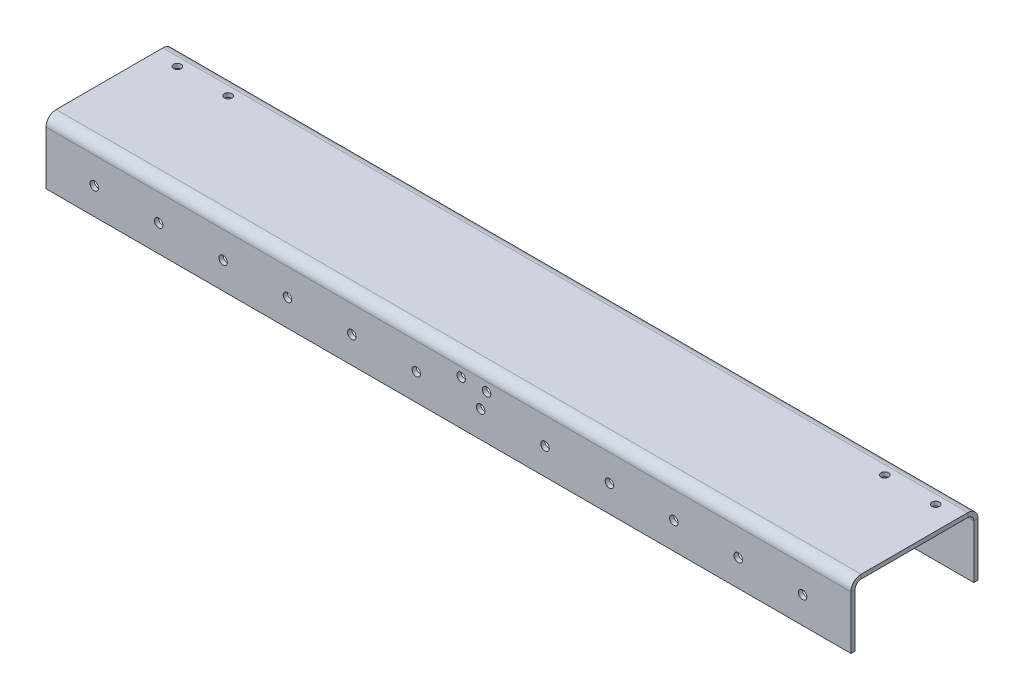
SolidWorks part; units mm, degrees
note: The reader was unsure of these and kept them because the rebuilt part matched: flange length of "Edge-Flange1".
material "Plain Carbon Steel"
ref_plane "Front Plane" through (0, 0, 0) normal (0, 0, 1) x (1, 0, 0)
ref_plane "Top Plane" through (0, 0, 0) normal (0, 1, 0) x (1, 0, 0)
ref_plane "Right Plane" through (0, 0, 0) normal (1, 0, 0) x (0, 0, -1)
sketch "Sketch1" plane through (0, 0, 0) normal (0, 1, 0) x (1, 0, 0)
  line L1 (-950, -150) -> (950, -150)
  line L2 (-950, -150) -> (-950, 150)
  line L3 (-950, 150) -> (950, 150)
  line L4 (950, -150) -> (950, 150)
  line L5 (-950, -150) -> (950, 150) construction
  line L6 (-950, 150) -> (950, -150) construction
  point P0 (0, 0)
  dimension "D1" = 1900
  dimension "D2" = 300
base flange "Base-Flange1" sketch "Sketch1" thickness 10 reverse thickness direction no parameters "D1"=3
edge flange "Edge-Flange1" sketch "Sketch12" flange profiles "Sketch12", "Sketch13" flange angle 90 flange length 150 flange position material inside bend radius 14 thickness 10 relief rectangular parameters "D6"=10, "D8"=1
sketch "Sketch12" plane through (0, -10, 150) normal (0, 0, 1) x (-1, 0, 0)
  line L0 (950, 0) -> (-950, 0) construction
  line L1 (950, 0) -> (-950, 0)
  line L2 (-950, 0) -> (-950, 140)
  line L3 (-950, 140) -> (950, 140)
  line L4 (950, 140) -> (950, 0)
sketch "Sketch13" plane through (0, -10, -150) normal (0, 0, -1) x (1, 0, 0)
  line L0 (950, 0) -> (-950, 0) construction
  line L1 (950, 0) -> (-950, 0)
  line L2 (-950, 0) -> (-950, 140)
  line L3 (-950, 140) -> (950, 140)
  line L4 (950, 140) -> (950, 0)
bend "EdgeBend1" bend radius 14 bend angle 90 parameters "D5"=1
bend "EdgeBend2" bend radius 14 bend angle 90 parameters "D5"=2
sketch "Sketch14" plane through (0, 0, 150) normal (0, 0, 1) x (1, 0, 0)
  line L0 (-950, -150) -> (-950, -10) construction
  line L1 (-950, -24) -> (-950, -150) construction
  circle A0 centre (-836, -87) radius 10
  point P7 (-950, -87)
  dimension "D1" = 20
  dimension "D2" = 114
extrude "Cut-Extrude1" cut sketch "Sketch14" against normal through all
pattern_linear "LPattern1" count 12 spacing 152 along (1, 0, 0) of "Cut-Extrude1"
sketch "Sketch16" plane through (0, 0, 150) normal (0, 0, 1) x (1, 0, 0)
  circle A0 centre (30, -45) radius 10
  circle A1 centre (90, -45) radius 10
  dimension "D1" = 20
  dimension "D3" = 30
  dimension "D2" = 45
  dimension "D4" = 60
extrude "Cut-Extrude2" cut sketch "Sketch16" against normal through all
sketch "Sketch17" plane through (0, 0, 0) normal (0, 1, 0) x (1, 0, 0)
  line L0 (950, 150) -> (-950, 150) construction
  line L1 (950, -126) -> (950, 126) construction
  circle A0 centre (775, 105) radius 9
  circle A1 centre (895, 105) radius 9
  dimension "D1" = 18
  dimension "D2" = 45
  dimension "D3" = 120
  dimension "D4" = 55
extrude "Cut-Extrude3" cut sketch "Sketch17" against normal through all
mirror "Mirror1" about plane through (0, 0, 0) normal (1, 0, 0) of "Cut-Extrude3"
sketch "Bend-Lines1" [suppressed] plane through (0, 0, 0) normal (0, 1, 0) x (1, 0, 0)
sketch "Bounding-Box1" [suppressed] plane through (0, 0, 0) normal (0, 1, 0) x (1, 0, 0)
sheet metal parameters "Sheet-Metal2" thickness 10 parameters "D1"=3
flat pattern "Flat-Pattern2" [suppressed]
sketch "Bend-Lines2" plane through (0, 0, 0) normal (0, 1, 0) x (1, 0, 0)
sketch3d "Bounding-Box2" [suppressed]
  line L0 (-950, 300, 0) -> (950, 300, 0) construction
  line L1 (-950, -300, 0) -> (950, -300, 0) construction
  line L2 (-950, 300, 0) -> (-950, -300, 0) construction
  line L3 (950, 300, 0) -> (950, -300, 0) construction
sheet metal parameters "Sheet-Metal3" thickness 10 parameters "D1"=3
flat pattern "Flat-Pattern2"
sketch "Bend-Lines2" plane through (0, 0, 0) normal (0, 1, 0) x (1, 0, 0)
  line L0 (950, 141.781) -> (-950, 141.781) construction
  line L1 (-950, -141.781) -> (950, -141.781) construction
  line L2 (950, 141.781) -> (-950, 141.781) construction
  line L3 (-950, -141.781) -> (950, -141.781) construction
sketch3d "Bounding-Box2" [suppressed]
  line L0 (950, 283.5619, 0) -> (-950, 283.5619, 0) construction
  line L1 (950, -283.5619, 0) -> (-950, -283.5619, 0) construction
  line L2 (950, 283.5619, 0) -> (950, -283.5619, 0) construction
  line L3 (-950, 283.5619, 0) -> (-950, -283.5619, 0) construction
bend of the flat pattern "Flatten-<EdgeBend1>1"
bend of the flat pattern "Flatten-<EdgeBend2>1"
sheet metal parameters "Sheet-Metal4" thickness 10 parameters "D1"=3
flat pattern "Flat-Pattern2"
sketch "Bend-Lines2" plane through (0, 0, 0) normal (0, 1, 0) x (1, 0, 0)
  line L0 (950, 141.781) -> (-950, 141.781) construction
  line L1 (-950, -141.781) -> (950, -141.781) construction
  line L2 (950, 141.781) -> (-950, 141.781) construction
  line L3 (-950, -141.781) -> (950, -141.781) construction
sketch3d "Bounding-Box2" [suppressed]
  line L0 (950, 283.5619, 0) -> (-950, 283.5619, 0) construction
  line L1 (950, -283.5619, 0) -> (-950, -283.5619, 0) construction
  line L2 (950, 283.5619, 0) -> (950, -283.5619, 0) construction
  line L3 (-950, 283.5619, 0) -> (-950, -283.5619, 0) construction
bend of the flat pattern "Flatten-<EdgeBend1>1"
bend of the flat pattern "Flatten-<EdgeBend2>1"
sheet metal parameters "Sheet-Metal5" thickness 10 parameters "D1"=3
flat pattern "Flat-Pattern2"
sketch "Bend-Lines2" plane through (0, 0, 0) normal (0, 1, 0) x (1, 0, 0)
  line L0 (950, 140.9226) -> (-950, 140.9226) construction
  line L1 (-950, -140.9226) -> (950, -140.9226) construction
  line L2 (950, 140.9226) -> (-950, 140.9226) construction
  line L3 (-950, -140.9226) -> (950, -140.9226) construction
sketch3d "Bounding-Box2" [suppressed]
  line L0 (950, 281.8451, 0) -> (-950, 281.8451, 0) construction
  line L1 (950, -281.8451, 0) -> (-950, -281.8451, 0) construction
  line L2 (950, 281.8451, 0) -> (950, -281.8451, 0) construction
  line L3 (-950, 281.8451, 0) -> (-950, -281.8451, 0) construction
bend of the flat pattern "Flatten-<EdgeBend1>1"
bend of the flat pattern "Flatten-<EdgeBend2>1"
sheet metal parameters "Sheet-Metal7" thickness 10 parameters "D1"=3
flat pattern "Flat-Pattern2"
sketch "Bend-Lines2" plane through (0, 0, 0) normal (0, 1, 0) x (1, 0, 0)
  line L0 (950, 140.9226) -> (-950, 140.9226) construction
  line L1 (-950, -140.9226) -> (950, -140.9226) construction
  line L2 (950, 140.9226) -> (-950, 140.9226) construction
  line L3 (-950, -140.9226) -> (950, -140.9226) construction
sketch3d "Bounding-Box2" [suppressed]
  line L0 (950, 281.8451, 0) -> (-950, 281.8451, 0) construction
  line L1 (950, -281.8451, 0) -> (-950, -281.8451, 0) construction
  line L2 (950, 281.8451, 0) -> (950, -281.8451, 0) construction
  line L3 (-950, 281.8451, 0) -> (-950, -281.8451, 0) construction
bend of the flat pattern "Flatten-<EdgeBend1>1"
bend of the flat pattern "Flatten-<EdgeBend2>1"
sheet metal parameters "Sheet-Metal8" thickness 10 parameters "D1"=3
flat pattern "Flat-Pattern2"
sketch "Bend-Lines2" plane through (0, 0, 0) normal (0, 1, 0) x (1, 0, 0)
  line L0 (950, 140.9226) -> (-950, 140.9226) construction
  line L1 (-950, -140.9226) -> (950, -140.9226) construction
  line L2 (950, 140.9226) -> (-950, 140.9226) construction
  line L3 (-950, -140.9226) -> (950, -140.9226) construction
sketch3d "Bounding-Box2" [suppressed]
  line L0 (950, 281.8451, 0) -> (-950, 281.8451, 0) construction
  line L1 (950, -281.8451, 0) -> (-950, -281.8451, 0) construction
  line L2 (950, 281.8451, 0) -> (950, -281.8451, 0) construction
  line L3 (-950, 281.8451, 0) -> (-950, -281.8451, 0) construction
bend of the flat pattern "Flatten-<EdgeBend1>1"
bend of the flat pattern "Flatten-<EdgeBend2>1"
sheet metal parameters "Sheet-Metal9" thickness 10 parameters "D1"=3
flat pattern "Flat-Pattern2"
sketch "Bend-Lines2" plane through (0, 0, 0) normal (0, 1, 0) x (1, 0, 0)
  line L0 (950, 140.9226) -> (-950, 140.9226) construction
  line L1 (-950, -140.9226) -> (950, -140.9226) construction
  line L2 (950, 140.9226) -> (-950, 140.9226) construction
  line L3 (-950, -140.9226) -> (950, -140.9226) construction
sketch3d "Bounding-Box2" [suppressed]
  line L0 (950, 281.8451, 0) -> (-950, 281.8451, 0) construction
  line L1 (950, -281.8451, 0) -> (-950, -281.8451, 0) construction
  line L2 (950, 281.8451, 0) -> (950, -281.8451, 0) construction
  line L3 (-950, 281.8451, 0) -> (-950, -281.8451, 0) construction
bend of the flat pattern "Flatten-<EdgeBend1>1"
bend of the flat pattern "Flatten-<EdgeBend2>1"
